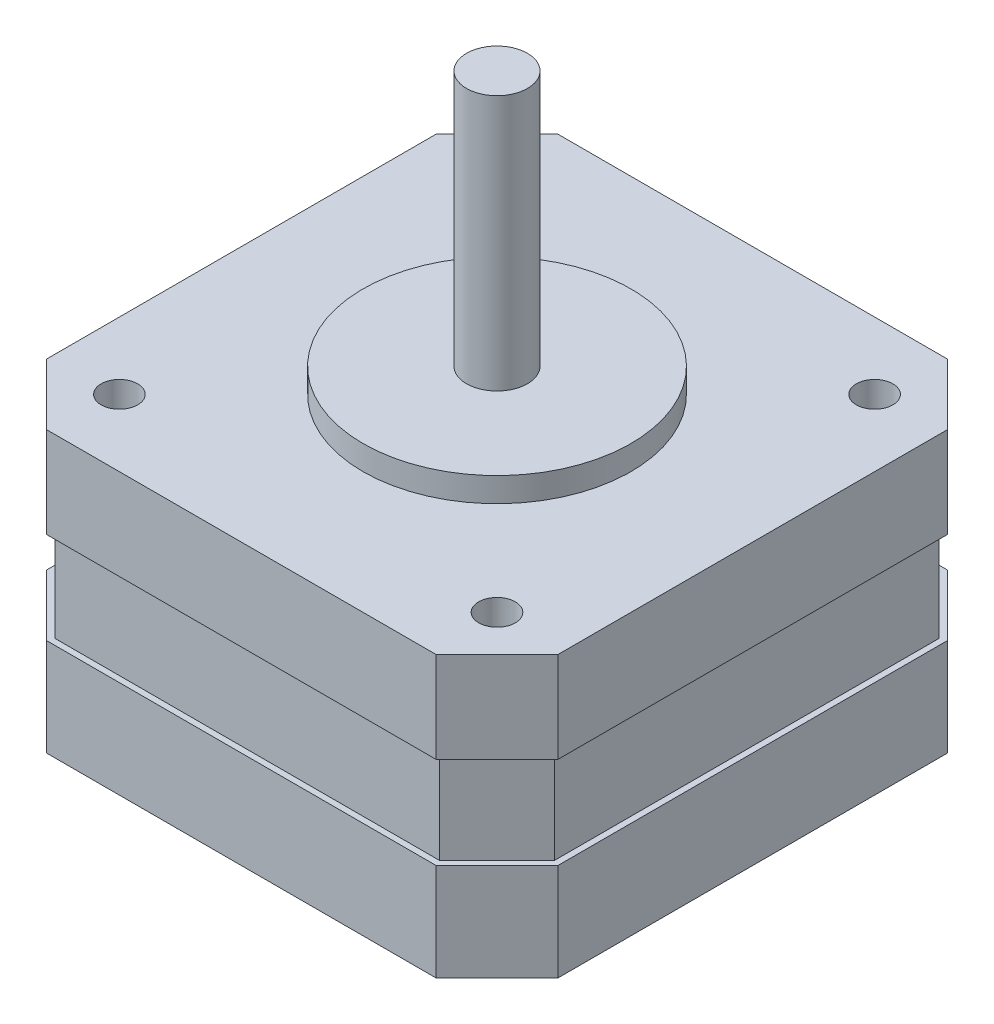
SolidWorks part; units mm, degrees
ref_plane "Спереди" through (0, 0, 0) normal (0, 0, 1) x (1, 0, 0)
ref_plane "Сверху" through (0, 0, 0) normal (0, 1, 0) x (1, 0, 0)
ref_plane "Справа" through (0, 0, 0) normal (1, 0, 0) x (0, 0, -1)
sketch "Эскиз1" plane through (0, 0, 0) normal (0, 1, 0) x (1, 0, 0)
  line L0 (-21, -16) -> (-16, -21)
  line L1 (-15.5, -15.5) -> (15.5, -15.5)
  line L2 (-15.5, -15.5) -> (-15.5, 15.5)
  line L3 (-15.5, 15.5) -> (15.5, 15.5)
  line L4 (15.5, -15.5) -> (15.5, 15.5)
  line L5 (-15.5, -15.5) -> (15.5, 15.5) construction
  line L6 (-15.5, 15.5) -> (15.5, -15.5) construction
  line L7 (-16, -21) -> (16, -21)
  line L8 (-21, -16) -> (-21, 16)
  line L9 (-16, 21) -> (16, 21)
  line L10 (21, -16) -> (21, 16)
  line L11 (-21, -21) -> (21, 21) construction
  line L12 (-21, 21) -> (21, -21) construction
  line L13 (-21, 16) -> (-16, 21)
  line L14 (16, 21) -> (21, 16)
  line L15 (16, -21) -> (21, -16)
  circle A0 centre (0, 0) radius 11
  circle A1 centre (-15.5, -15.5) radius 1.5
  circle A2 centre (0, 0) radius 2.5
  circle A3 centre (-15.5, 15.5) radius 1.5
  circle A4 centre (15.5, 15.5) radius 1.5
  circle A5 centre (15.5, -15.5) radius 1.5
  point P0 (0, 0)
  point P6 (0, 0)
  dimension "D3" = 22
  dimension "D4" = 5
  dimension "D12" = 3
  dimension "D1" = 42
  dimension "D2" = 31
  dimension "D5" = 5
  dimension "D6" = 45
  dimension "D8" = 5
  dimension "D9" = 45
  dimension "D10" = 5
  dimension "D11" = 45
  dimension "D13" = 42
extrude "Бобышка-Вытянуть1" add sketch "Эскиз1" against normal blind 23 contours L8 L13 L9 L14 L10 L15 L7 L0
extrude "Бобышка-Вытянуть2" add sketch "Эскиз1<3>" along normal blind 23 contours A2 region at (0, 0, 0)
sketch "Эскиз1<3>" plane through (0, 0, 0) normal (0, 1, 0) x (1, 0, 0) same geometry as "Эскиз1"
extrude "Бобышка-Вытянуть3" add sketch "Эскиз1<4>" along normal blind 2 contours A0 A2 region at (-10.6889, 0, 0)
sketch "Эскиз1<4>" plane through (0, 0, 0) normal (0, 1, 0) x (1, 0, 0) same geometry as "Эскиз1"
extrude "Вырез-Вытянуть1" cut sketch "Эскиз1<5>" against normal blind 10 contours L2 A1 L1 | L1 A1 L2 | L3 A3 L2 | L2 A3 L3 | L3 A4 L4 | L4 A4 L3 | L4 A5 L1 | L1 A5 L4 region at (-14.8634, 0, 14.8634) region at (-15.7122, 0, 15.7122) region at (14.8634, 0, 14.8634) region at (15.7122, 0, 15.7122) region at (-15.7122, 0, -15.7122) region at (-14.8634, 0, -14.8634) region at (14.8634, 0, -14.8634) region at (15.7122, 0, -15.7122)
sketch "Эскиз1<5>" plane through (0, 0, 0) normal (0, 1, 0) x (1, 0, 0) same geometry as "Эскиз1"
sketch "Эскиз2" plane through (0, 0, -21) normal (0, 0, -1) x (-1, 0, 0)
  line L0 (-16, -23) -> (-16, 0) construction
  line L1 (-16, -7.4567) -> (16, -7.4567)
  line L2 (-16, -7.4567) -> (-16, -15)
  line L3 (-16, -15) -> (16, -15)
  line L4 (16, -7.4567) -> (16, -15)
  line L5 (16, -23) -> (16, 0) construction
  line L6 (16, 0) -> (-16, 0) construction
  dimension "D1" = 15
sketch "Эскиз3" plane through (18.5, 0, -18.5) normal (0.7071, 0, -0.7071) x (-0.7071, 0, -0.7071)
  line L0 (-3.5355, -23) -> (-3.5355, 0) construction
  line L1 (-3.5355, -15) -> (3.5355, -15)
  line L2 (-3.5355, -15) -> (-3.5355, -7.4567)
  line L3 (-3.5355, -7.4567) -> (3.5355, -7.4567)
  line L4 (3.5355, -15) -> (3.5355, -7.4567)
  line L5 (3.5355, 0) -> (-3.5355, 0) construction
  dimension "D1" = 15
sketch "Эскиз4" plane through (21, 0, 0) normal (1, 0, 0) x (0, 0, -1)
  line L0 (-16, -23) -> (-16, 0) construction
  line L1 (16, -15) -> (-16, -15)
  line L2 (16, -15) -> (16, -7.4567)
  line L3 (16, -7.4567) -> (-16, -7.4567)
  line L4 (-16, -15) -> (-16, -7.4567)
  line L5 (16, -7.4567) -> (21, -7.4567) construction
sketch "Эскиз5" plane through (18.5, 0, 18.5) normal (0.7071, 0, 0.7071) x (0.7071, 0, -0.7071)
  line L0 (-3.5355, -23) -> (-3.5355, 0) construction
  line L1 (3.5355, -15) -> (-3.5355, -15)
  line L2 (3.5355, -15) -> (3.5355, -7.4567)
  line L3 (3.5355, -7.4567) -> (-3.5355, -7.4567)
  line L4 (-3.5355, -15) -> (-3.5355, -7.4567)
  line L5 (26.163, -7.4567) -> (3.5355, -7.4567) construction
sketch "Эскиз6" plane through (0, 0, 21) normal (0, 0, 1) x (1, 0, 0)
  line L0 (-16, -23) -> (-16, 0) construction
  line L1 (16, -15) -> (-16, -15)
  line L2 (16, -15) -> (16, -7.4567)
  line L3 (16, -7.4567) -> (-16, -7.4567)
  line L4 (-16, -15) -> (-16, -7.4567)
  line L5 (21, -7.4567) -> (16, -7.4567) construction
sketch "Эскиз7" plane through (-18.5, 0, 18.5) normal (-0.7071, 0, 0.7071) x (0.7071, 0, 0.7071)
  line L0 (-3.5355, -23) -> (-3.5355, 0) construction
  line L1 (3.5355, -15) -> (-3.5355, -15)
  line L2 (3.5355, -15) -> (3.5355, -7.4567)
  line L3 (3.5355, -7.4567) -> (-3.5355, -7.4567)
  line L4 (-3.5355, -15) -> (-3.5355, -7.4567)
  line L5 (26.163, -7.4567) -> (3.5355, -7.4567) construction
sketch "Эскиз8" plane through (-21, 0, 0) normal (-1, 0, 0) x (0, 0, 1)
  line L0 (-16, -23) -> (-16, 0) construction
  line L1 (16, -15) -> (-16, -15)
  line L2 (16, -15) -> (16, -7.4567)
  line L3 (16, -7.4567) -> (-16, -7.4567)
  line L4 (-16, -15) -> (-16, -7.4567)
  line L5 (21, -7.4567) -> (16, -7.4567) construction
sketch "Эскиз9" plane through (-18.5, 0, -18.5) normal (-0.7071, 0, -0.7071) x (-0.7071, 0, 0.7071)
  line L1 (3.5355, -15) -> (-3.5355, -15)
  line L2 (3.5355, -15) -> (3.5355, -7.4567)
  line L3 (3.5355, -7.4567) -> (-3.5355, -7.4567)
  line L4 (-3.5355, -15) -> (-3.5355, -7.4567)
extrude "Вырез-Вытянуть2" cut sketch "Эскиз2" against normal blind 0.5
extrude "Вырез-Вытянуть3" cut sketch "Эскиз9" against normal blind 0.5
extrude "Вырез-Вытянуть4" cut sketch "Эскиз8" against normal blind 0.5
extrude "Вырез-Вытянуть5" cut sketch "Эскиз7" against normal blind 0.5
extrude "Вырез-Вытянуть6" cut sketch "Эскиз6" against normal blind 0.5
extrude "Вырез-Вытянуть7" cut sketch "Эскиз5" against normal blind 0.5
extrude "Вырез-Вытянуть8" cut sketch "Эскиз4" against normal blind 0.5
extrude "Вырез-Вытянуть9" cut sketch "Эскиз3" against normal blind 0.5
